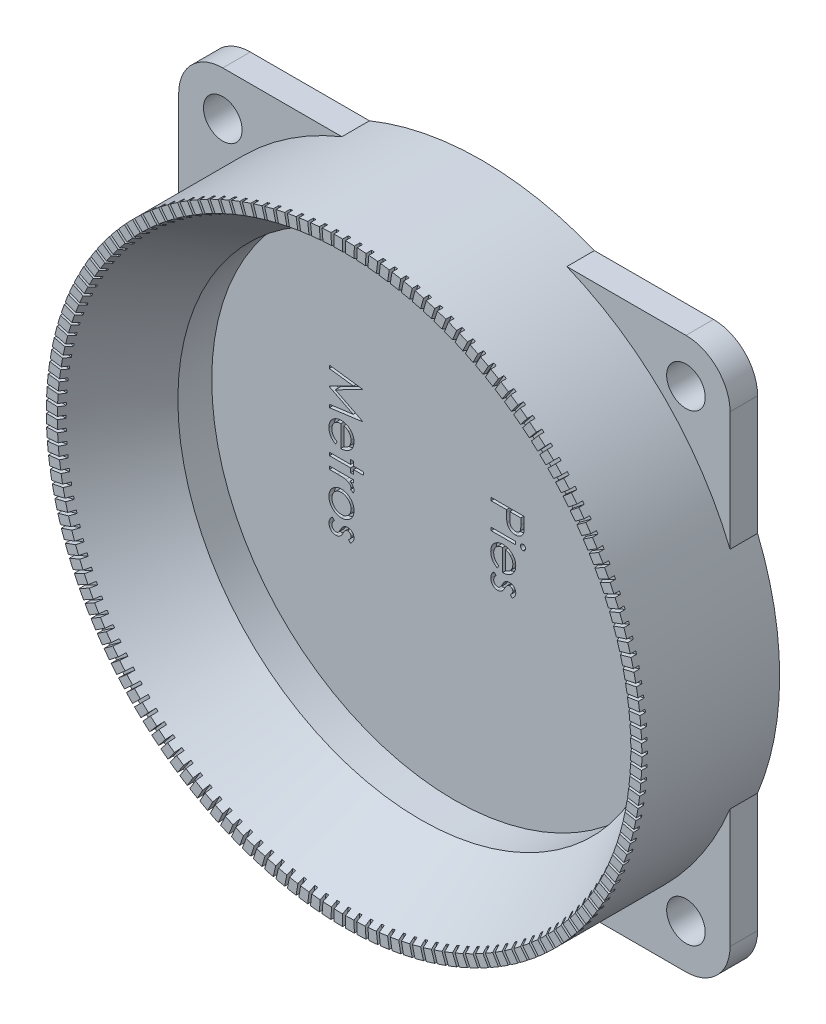
SolidWorks part; units mm, degrees
ref_plane "Alzado" through (0, 0, 0) normal (0, 0, 1) x (1, 0, 0)
ref_plane "Planta" through (0, 0, 0) normal (0, 1, 0) x (1, 0, 0)
ref_plane "Vista lateral" through (0, 0, 0) normal (1, 0, 0) x (0, 0, -1)
sketch "Croquis1" plane through (0, 0, 0) normal (0, 0, 1) x (1, 0, 0)
  line L0 (0, 50) -> (0, -50) construction
  line L1 (-42, -50) -> (42, -50)
  line L2 (-50, -42) -> (-50, 42)
  line L3 (-42, 50) -> (42, 50)
  line L4 (50, -42) -> (50, 42)
  line L5 (-50, -50) -> (50, 50) construction
  line L6 (-50, 50) -> (50, -50) construction
  line L7 (50, 0) -> (-50, 0) construction
  circle A3 centre (-42, 42) radius 3.5
  circle A5 centre (42, 42) radius 3.5
  circle A8 centre (42, -42) radius 3.5
  circle A10 centre (-42, -42) radius 3.5
  arc A15 (-42, 50) -> (-50, 42) centre (-42, 42) ccw
  arc A16 (50, 42) -> (42, 50) centre (42, 42) ccw
  arc A17 (50, -42) -> (42, -50) centre (42, -42) cw
  arc A18 (-42, -50) -> (-50, -42) centre (-42, -42) cw
  point P0 (0, 0)
  point P12 (-30.6742, -30.6742)
  point P13 (-30, -30)
  dimension "D1" = 100
  dimension "D2" = 7
  dimension "D3" = 8
extrude "Saliente-Extruir1" add sketch "Croquis1" along normal blind 5
sketch "Croquis2" plane through (0, 0, 5) normal (0, 0, 1) x (1, 0, 0)
  circle A2 centre (0, 0) radius 54
  circle A3 centre (0, 0) radius 44
  dimension "D1" = 108
  dimension "D2" = 10
extrude "Saliente-Extruir2" add sketch "Croquis2" along normal blind 20 and the other way blind 5
chamfer "Chaflán1" distance 8 angle 60 1 edges at (44, 0, 25) first distance on face at (54, 0, 25)
sketch "Croquis3" plane through (0, 0, 25) normal (0, 0, 1) x (1, 0, 0)
  line L0 (0, 0) -> (-59.4744, 0) construction
  line L2 (-54.9173, 0.25) -> (-50.694, 0.25)
  line L3 (-54.9173, 0.25) -> (-54.9173, -0.25)
  line L4 (-54.9173, -0.25) -> (-50.694, -0.25)
  line L5 (-50.694, 0.25) -> (-50.694, -0.25)
  point P7 (-50.694, 0)
  dimension "D1" = 0.5
extrude "Cortar-Extruir1" cut sketch "Croquis3" against normal blind 1
pattern_circular "MatrizC1" count 160 over 360 about axis through (0, 0, 25) along (0, 0, -1) of "Cortar-Extruir1"
sketch "Croquis4" plane through (0, 0, 5) normal (0, 0, 1) x (1, 0, 0)
  line L0 (-44, 17.551) -> (-44, -17.551) construction
  line L4 (-29.3333, 32.7957) -> (-29.3333, -32.7957) construction
  line L5 (-14.6633, 41.4848) -> (-14.6633, -41.4848) construction
  line L6 (0.0067, 44) -> (0.0067, -44) construction
  line L7 (14.6767, 41.4801) -> (14.6767, -41.4801) construction
  line L8 (29.3467, 32.7837) -> (29.3467, -32.7837) construction
  line L9 (44.0167, 0) -> (44.0167, -10.8929) construction
  line L10 (-31.9605, 0) -> (-17.2905, 0) construction
  line L11 (60.8474, 0) -> (-68.7625, 0) construction
  line L12 (36.0167, 22.6537) -> (36.0167, -22.6537) construction
  line L13 (6.6767, 25.4717) -> (6.6767, -25.4717) construction
  line L14 (-22.6633, 28.9572) -> (-22.6633, -28.9572) construction
  circle A2 centre (0, 0) radius 44 construction
  circle A3 centre (0, 0) radius 44 construction
  text T0 "Millas" font "Century Gothic" height 6
  text T1 "Pies" font "Century Gothic" height 6
  text T2 "Metros" font "Century Gothic" height 6
  point P3 (-44, 0)
  point P26 (36.0167, 0)
  point P30 (6.6767, 0)
  point P31 (6.6767, 0)
  point P35 (-22.6633, 0)
  dimension "D1" = 14.6667
  dimension "D3" = 14.67
  dimension "D4" = 8
  dimension "D5" = 8
  dimension "D6" = 8
  dimension "D2" = 6
extrude "Cortar-Extruir2" cut sketch "Croquis4" against normal blind 1
